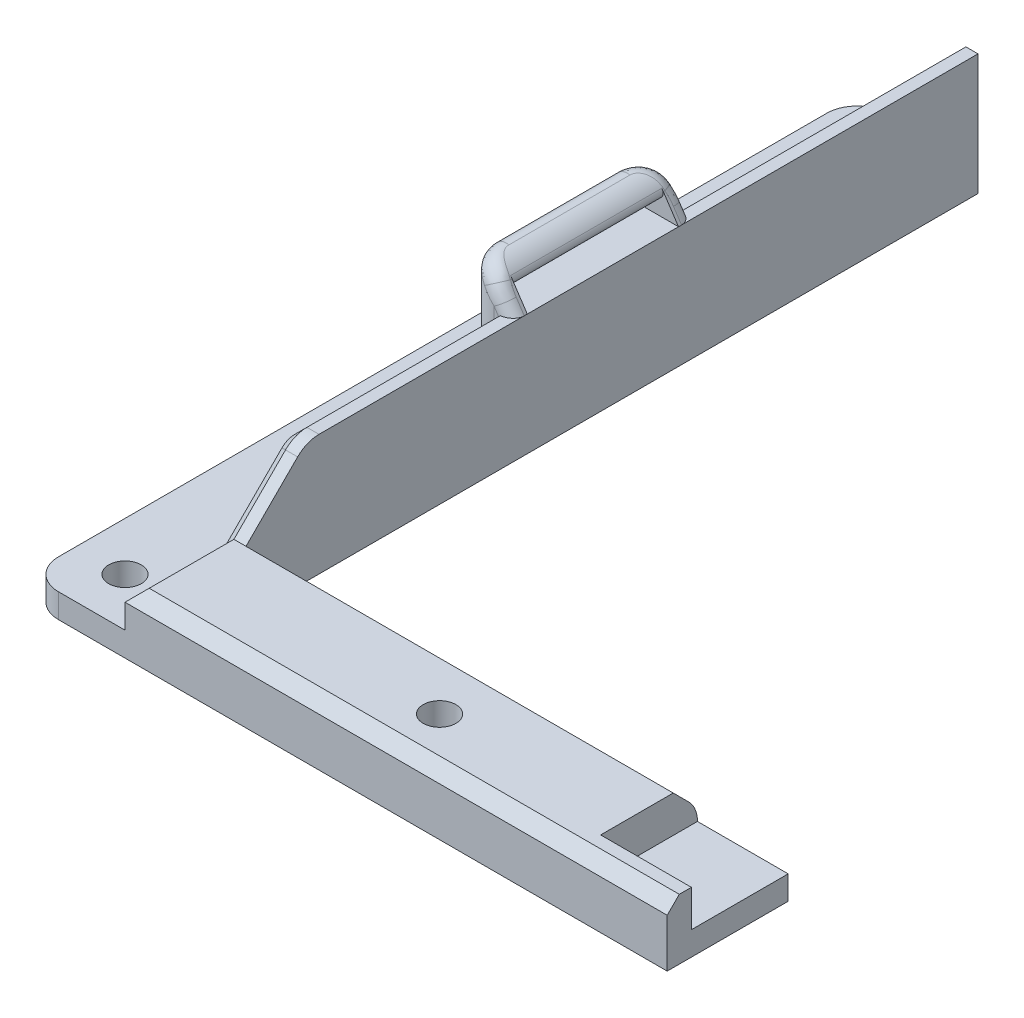
SolidWorks part; units mm, degrees
ref_plane "Front Plane" through (0, 0, 0) normal (0, 0, 1) x (1, 0, 0)
ref_plane "Top Plane" through (0, 0, 0) normal (0, 1, 0) x (1, 0, 0)
ref_plane "Right Plane" through (0, 0, 0) normal (1, 0, 0) x (0, 0, -1)
sketch "Sketch1" plane through (0, 0, 0) normal (0, 1, 0) x (1, 0, 0)
  line L0 (204.7875, -25.4) -> (204.7875, 148.59)
  line L1 (0, 0) -> (179.3875, 0)
  line L2 (0, 0) -> (0, 148.59)
  line L3 (-25.4, -25.4) -> (204.7875, -25.4)
  line L4 (179.3875, 0) -> (179.3875, 148.59)
  line L5 (-25.4, -25.4) -> (-25.4, 148.59)
  line L6 (204.7875, 148.59) -> (179.3875, 148.59)
  line L7 (0, 148.59) -> (-25.4, 148.59)
  dimension "D1" = 179.3875
  dimension "D2" = 148.59
  dimension "D3" = 148.59
  dimension "D4" = 25.4
extrude "Boss-Extrude1" add sketch "Sketch1" along normal blind 5.08
sketch "Sketch2" plane through (0, 5.08, 0) normal (0, 1, 0) x (1, 0, 0)
  line L6 (184.4675, 148.59) -> (179.3875, 148.59)
  line L7 (179.3875, 148.59) -> (179.3875, 0)
  line L8 (179.3875, 0) -> (0, 0)
  line L9 (184.4675, 148.59) -> (184.4675, -5.08)
  line L10 (184.4675, -5.08) -> (-5.08, -5.08)
  line L11 (-5.08, -5.08) -> (-5.08, 148.59)
  line L12 (184.4675, 148.59) -> (184.4675, -5.08)
  line L13 (184.4675, -5.08) -> (-5.08, -5.08)
  line L14 (-5.08, -5.08) -> (-5.08, 148.59)
  line L15 (0, 0) -> (0, 148.59)
  line L16 (0, 148.59) -> (-5.08, 148.59)
  dimension "D1" = 5.08
extrude "Boss-Extrude2" add sketch "Sketch2" along normal blind 20.32
fillet "Fillet1" radius 6.35 4 edges at (204.7875, 2.54, -148.59) (204.7875, 2.54, 25.4) (-25.4, 2.54, 25.4) (-25.4, 2.54, -148.59)
sketch "Sketch3" plane through (0, 5.08, 0) normal (0, 1, 0) x (1, 0, 0)
  line L0 (-5.08, 148.59) -> (-5.08, -5.08) construction
  line L1 (-5.08, 88.9) -> (-10.16, 88.9)
  line L2 (-5.08, 88.9) -> (-5.08, 50.8)
  line L3 (-5.08, 50.8) -> (-10.16, 50.8)
  line L4 (-10.16, 88.9) -> (-10.16, 50.8)
  line L5 (184.4675, -5.08) -> (184.4675, 148.59) construction
  line L6 (184.4675, 50.8) -> (189.5475, 50.8)
  line L7 (184.4675, 50.8) -> (184.4675, 88.9)
  line L8 (184.4675, 88.9) -> (189.5475, 88.9)
  line L9 (189.5475, 50.8) -> (189.5475, 88.9)
  line L10 (-19.05, -25.4) -> (198.4375, -25.4) construction
  dimension "D1" = 38.1
  dimension "D2" = 38.1
  dimension "D3" = 76.2
  dimension "D4" = 76.2
  dimension "D5" = 5.08
  dimension "D6" = 5.08
extrude "Boss-Extrude3" add sketch "Sketch3" along normal blind 27.94
sketch "Sketch4" plane through (0, 0, -88.9) normal (0, 0, -1) x (-1, 0, 0)
  line L0 (-184.4675, 33.02) -> (-179.3875, 25.4)
  line L1 (-179.3875, 25.4) -> (-184.4675, 25.4)
  line L2 (-184.4675, 25.4) -> (-184.4675, 33.02)
  line L3 (5.08, 33.02) -> (0, 25.4)
  line L4 (5.08, 25.4) -> (-184.4675, 25.4) construction
  line L5 (-179.3875, 25.4) -> (0, 25.4) construction
  line L6 (0, 25.4) -> (5.08, 25.4)
  line L7 (5.08, 25.4) -> (5.08, 33.02)
extrude "Boss-Extrude4" add sketch "Sketch4" against normal up to surface (38.1 mm away) up to face at (-7.112, 20.32, -50.8)
sketch "Sketch5" plane through (189.5475, 0, 0) normal (1, 0, 0) x (0, 0, -1)
  line L0 (-5.08, 25.4) -> (50.8, 25.4) construction
  line L1 (53.975, 25.4) -> (85.725, 25.4)
  line L2 (53.975, 25.4) -> (53.975, 28.575)
  line L3 (53.975, 28.575) -> (85.725, 28.575)
  line L4 (85.725, 25.4) -> (85.725, 28.575)
  line L5 (50.8, 33.02) -> (50.8, 5.08) construction
  dimension "D1" = 0
  dimension "D2" = 3.175
  dimension "D3" = 31.75
  dimension "D4" = 3.175
extrude "Cut-Extrude1" cut sketch "Sketch5" against normal through all both and the other way through all
sketch "Sketch6" plane through (0, 0, 0) normal (0, 0, -1) x (-1, 0, 0)
  line L0 (0, 25.4) -> (0, 0) construction
  line L1 (-179.3875, 25.4) -> (0, 25.4)
  line L2 (-179.3875, 25.4) -> (-179.3875, 12.7)
  line L3 (-179.3875, 12.7) -> (0, 12.7)
  line L4 (0, 25.4) -> (0, 12.7)
extrude "Cut-Extrude2" cut sketch "Sketch6" against normal through all
sketch "Sketch8" plane through (179.3875, 0, 0) normal (-1, 0, 0) x (0, 0, 1)
  line L0 (5.08, 12.7) -> (0, 7.62)
  line L1 (0, 7.62) -> (0, 12.7)
  line L2 (0, 12.7) -> (5.08, 12.7)
extrude "Cut-Extrude3" cut sketch "Sketch8" along normal up to surface (179.3875 mm away) up to face at (0, 17.78, -56.642)
sketch "Sketch9" plane through (184.4675, 0, 0) normal (1, 0, 0) x (0, 0, -1)
  line L0 (-5.08, 12.7) -> (7.62, 25.4)
  line L1 (-5.08, 25.4) -> (50.8, 25.4) construction
  line L2 (7.62, 25.4) -> (-5.08, 25.4)
  line L3 (-5.08, 25.4) -> (-5.08, 12.7)
  dimension "D1" = 45
extrude "Cut-Extrude4" cut sketch "Sketch9" against normal through all both and the other way through all
fillet "Fillet3" radius 6.35 1 edges at (89.6938, 7.62, 0)
fillet "Fillet4" radius 6.35 8 edges at (-10.16, 19.05, -88.9) (-10.16, 19.05, -50.8) (189.5475, 19.05, -88.9) (189.5475, 19.05, -50.8) (-5.08, 33.02, -69.85) (184.4675, 33.02, -69.85) (-2.54, 25.4, -7.62) (181.9275, 25.4, -7.62)
fillet "Fillet5" radius 1.27 8 edges at (-2.1167, 28.575, -69.85) (181.5042, 28.575, -69.85) (189.3311, 28.575, -55.5065) (189.3311, 28.575, -84.1935) (-9.9436, 28.575, -84.1935) (-9.9436, 28.575, -55.5065) (189.5475, 28.575, -69.85) (-10.16, 28.575, -69.85)
sketch "Sketch10" plane through (-5.08, 0, 0) normal (-1, 0, 0) x (0, 0, 1)
  line L1 (5.08, 12.7) -> (25.4, 12.7)
  line L2 (5.08, 12.7) -> (5.08, 5.08)
  line L3 (5.08, 5.08) -> (25.4, 5.08)
  line L4 (25.4, 12.7) -> (25.4, 5.08)
extrude "Boss-Extrude5" add sketch "Sketch10" against normal up to surface (189.5475 mm away) up to face at (184.4675, 16.2744, -13.253)
chamfer "Chamfer1" distance 2.54 angle 45 1 edges at (89.6938, 12.7, 25.4)
chamfer "Chamfer2" distance 2.54 angle 45 8 edges at (184.4675, 25.4, -118.6809) (184.4675, 24.9166, -7.8202) (184.4675, 18.1201, -0.3401) (184.4675, 12.7, 13.97) (-5.08, 12.7, 13.97) (-5.08, 25.4, -118.6809) (-5.08, 24.9166, -7.8202) (-5.08, 18.1201, -0.3401)
fillet "Fillet8" radius 2.54 14 edges at (-1.5974, 27.7962, -88.9) (-3.4871, 30.5955, -88.9) (-5.1252, 32.0624, -88.7623) (-9.7247, 33.02, -84.8606) (-1.5974, 27.7962, -50.8) (-3.4871, 30.5955, -50.8) (-5.1252, 32.0624, -50.9377) (180.9849, 27.7962, -50.8) (182.8746, 30.5955, -50.8) (184.5127, 32.0624, -50.9377) (189.1122, 33.02, -54.8394) (180.9849, 27.7962, -88.9) (182.8746, 30.5955, -88.9) (184.5127, 32.0624, -88.7623)
sketch "Sketch11" plane through (0, 5.08, 0) normal (0, 1, 0) x (1, 0, 0)
  line L0 (-25.4, 142.24) -> (-25.4, -19.05) construction
  line L1 (204.7875, -19.05) -> (204.7875, 142.24) construction
  line L2 (-5.08, 148.59) -> (-19.05, 148.59) construction
  line L4 (198.4375, 148.59) -> (184.4675, 148.59) construction
  line L5 (184.4675, -25.4) -> (198.4375, -25.4) construction
  line L6 (-19.05, -25.4) -> (-5.08, -25.4) construction
  line L7 (184.4675, -25.4) -> (-5.08, -25.4) construction
  circle A0 centre (-15.24, -15.24) radius 3.429
  circle A1 centre (194.6275, -15.24) radius 3.429
  circle A2 centre (194.6275, 97.79) radius 3.429
  circle A3 centre (-15.24, 97.79) radius 3.429
  circle A4 centre (50.8, -15.24) radius 3.429
  circle A5 centre (128.5875, -15.24) radius 3.429
  dimension "D1" = 6.858
  dimension "D2" = 6.858
  dimension "D3" = 6.858
  dimension "D4" = 6.858
  dimension "D15" = 6.858
  dimension "D16" = 6.858
  dimension "D5" = 10.16
  dimension "D6" = 10.16
  dimension "D7" = 10.16
  dimension "D8" = 10.16
  dimension "D9" = 50.8
  dimension "D10" = 50.8
  dimension "D11" = 10.16
  dimension "D12" = 10.16
  dimension "D13" = 10.16
  dimension "D14" = 10.16
  dimension "D17" = 76.2
  dimension "D18" = 76.2
extrude "Cut-Extrude5" cut sketch "Sketch11" against normal through all both and the other way through all
sketch "Sketch12" plane through (0, 12.7, 0) normal (0, 1, 0) x (1, 0, 0)
  line L0 (89.6937, -22.86) -> (89.6938, 0) construction
  line L1 (-2.54, -22.86) -> (181.9275, -22.86) construction
  line L2 (0, 0) -> (179.3875, 0) construction
  line L3 (89.6938, 0) -> (89.6938, -25.4) construction
  line L4 (184.4675, -25.4) -> (-5.08, -25.4) construction
  line L5 (89.6938, -25.4) -> (89.6938, 157.9407)
  line L6 (89.6938, 157.9407) -> (229.6045, 157.9407)
  line L7 (229.6045, 157.9407) -> (229.6045, -37.244)
  line L8 (229.6045, -37.244) -> (-47.4458, -37.244)
  line L9 (-47.4458, -37.244) -> (-47.4458, 157.9407)
  line L10 (-47.4458, 157.9407) -> (89.6938, 157.9407)
  line L11 (89.6938, -25.4) -> (89.6938, -37.244)
  circle M1 centre (128.5875, -15.24) radius 3.429
  line M3 (-2.54, -22.86) -> (181.9275, -22.86)
  line M4 (181.9275, -22.86) -> (181.9275, -5.08)
  line M5 (181.9275, -5.08) -> (179.3875, -5.08)
  line M6 (179.3875, -5.08) -> (0, -5.08)
extrude "Cut-Extrude8" cut sketch "Sketch12" against normal through all both and the other way through all contours L5 L11 L8 L7 L6 M6 M5 M4 M3 | L5 M3 M4 M5 M6 M1 region at (161.1721, 12.7, -65.0964) region at (135.9771, 12.7, 13.9407)
sketch "Sketch13" plane through (89.6938, 0, 0) normal (1, 0, 0) x (0, 0, -1)
  line L0 (-22.86, 12.7) -> (-5.08, 12.7) construction
  line L1 (0, 4.9897) -> (-20.32, 4.9897)
  line L2 (0, 4.9897) -> (0, 0)
  line L3 (0, 0) -> (-25.4, 0)
  line L4 (-25.4, 4.9897) -> (-25.4, 0)
  line L6 (-25.4, 4.9897) -> (-25.4, 10.16)
  line L7 (-22.86, 12.7) -> (-20.32, 12.7)
  line L8 (-20.32, 4.9897) -> (-20.32, 12.7)
  line L9 (-22.86, 12.7) -> (-25.4, 10.16)
  dimension "D1" = 5.08
  dimension "D2" = 135
extrude "Boss-Extrude6" add sketch "Sketch13" along normal blind 19.05
